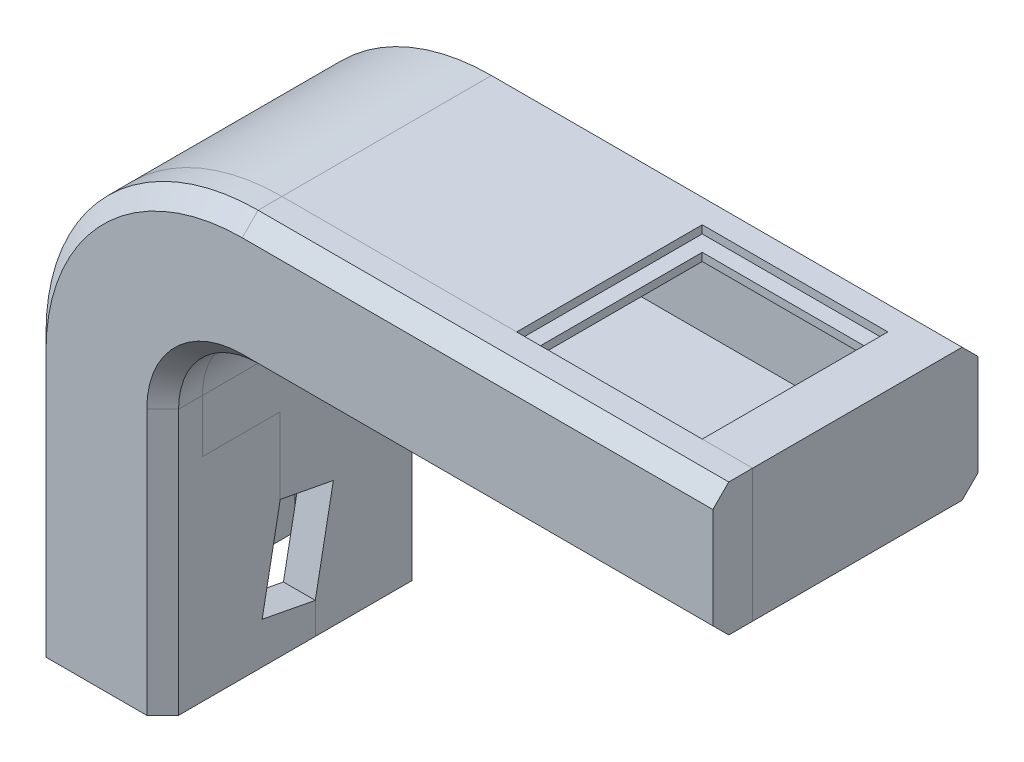
SolidWorks part; units mm, degrees
ref_plane "Front Plane" through (0, 0, 0) normal (0, 0, 1) x (1, 0, 0)
ref_plane "Top Plane" through (0, 0, 0) normal (0, 1, 0) x (1, 0, 0)
ref_plane "Right Plane" through (0, 0, 0) normal (1, 0, 0) x (0, 0, -1)
sketch "Sketch1" plane through (0, 0, 0) normal (0, 0, 1) x (1, 0, 0)
  line L1 (-76.75, 10) -> (-101.75, 10)
  line L2 (-76.75, 10) -> (-76.75, 100)
  line L3 (-76.75, 100) -> (-101.75, 100)
  line L4 (-101.75, 10) -> (-101.75, 100)
  line L5 (-76.75, 100) -> (27, 100)
  line L6 (-76.75, 100) -> (-76.75, 75)
  line L7 (-76.75, 75) -> (27, 75)
  line L8 (27, 100) -> (27, 75)
  dimension "D1" = 10
  dimension "D2" = 25
  dimension "D3" = 75
  dimension "D4" = 76.75
  dimension "D5" = 27
extrude "Boss-Extrude1" add sketch "Sketch1" along normal mid plane 50 contours L4 L1 L2 L3 | L8 L5 L2 L7 region at (-89.25, 55, 0) region at (-24.875, 87.5, 0)
fillet "Fillet2" radius 15 1 edges at (-76.75, 75, 0)
fillet "Fillet3" radius 40 1 edges at (-101.75, 100, 0)
fillet "Fillet1" radius 3 12 edges at (-17.375, 75, -25) (-17.375, 100, -25) (-17.375, 100, 25) (-17.375, 75, 25) (-101.75, 35, -25) (-101.75, 35, 25) (-76.75, 35, -25) (-76.75, 35, 25) (-90.0343, 88.2843, -25) (-90.0343, 88.2843, 25) (-72.3566, 70.6066, -25) (-72.3566, 70.6066, 25) profile chamfer
shell "Shell1" thickness 6 removed face at (-89.25, 10, 0)
sketch "Sketch2" plane through (-101.75, 0, 0) normal (-1, 0, 0) x (0, 0, 1)
  line L0 (-7.0749, 33.6959) -> (-5.199, 23.8734) construction
  line L1 (-5.6628, 15.6403) -> (8.0887, 18.2666) construction
  line L2 (4.6235, 25.7494) -> (2.7475, 35.5718) construction
  line L8 (11.8506, 16.9489) -> (9.9747, 26.7714) construction
  line L9 (9.9747, 26.7714) -> (-9.6702, 23.0195) construction
  line L10 (-9.6702, 23.0195) -> (-7.7943, 13.197) construction
  line L11 (-7.7943, 13.197) -> (11.8506, 16.9489) construction
  line L12 (9.9747, 26.7714) -> (8.0988, 36.5938) construction
  line L13 (8.0988, 36.5938) -> (-11.5462, 32.842) construction
  line L14 (-11.5462, 32.842) -> (-9.6702, 23.0195) construction
  line L15 (-9.6702, 23.0195) -> (9.9747, 26.7714) construction
  line L16 (-3.7777, 15.8985) -> (6.2412, 17.8119)
  line L17 (-3.7777, 15.8985) -> (-7.1919, 33.7754)
  line L18 (6.2412, 17.8119) -> (2.827, 35.6888)
  line L19 (-7.1919, 33.7754) -> (2.827, 35.6888)
  line L20 (-2.1637, 34.6339) -> (-2.1825, 34.7321) construction
  dimension "D1" = 0.1
  dimension "D2" = 0.1
  dimension "D3" = 0.1
  dimension "D4" = 0.1
extrude "Cut-Extrude1" cut sketch "Sketch2" against normal through all
ref_axis "Axis1" through (0, 164.2594, 0) along (0, -1, 0)
sketch "Sketch3" plane through (0, 100, 0) normal (0, 1, 0) x (1, 0, 0)
  line L0 (27, -22) -> (27, 22) construction
  line L1 (17.5, 17.5) -> (-17.5, 17.5)
  line L2 (17.5, 17.5) -> (17.5, -17.5)
  line L3 (17.5, -17.5) -> (-17.5, -17.5)
  line L4 (-17.5, 17.5) -> (-17.5, -17.5)
  point P6 (17.5, 0)
  point P9 (0, 17.5)
  dimension "D1" = 9.5
  dimension "D2" = 35
extrude "Cut-Extrude2" cut sketch "Sketch3" against normal up to next
sketch "Sketch4" plane through (0, 0, -17.5) normal (0, 0, 1) x (1, 0, 0)
  line L0 (-17.5, 94) -> (-17.5, 100) construction
  line L1 (-21.6, 98.5) -> (21.6, 98.5)
  line L2 (-21.6, 98.5) -> (-21.6, 95.5)
  line L3 (-21.6, 95.5) -> (21.6, 95.5)
  line L4 (21.6, 98.5) -> (21.6, 95.5)
  line L6 (17.5, 94) -> (17.5, 100) construction
  point P8 (-17.5, 97)
  point P9 (-21.6, 97)
  dimension "D1" = 3
  dimension "D2" = 4.1
  dimension "D3" = 4.1
extrude "Cut-Extrude3" cut sketch "Sketch4" against normal blind 4.1 and the other way blind 39.1
sketch "Sketch5" plane through (0, 75, 0) normal (0, -1, 0) x (1, 0, 0)
  line L0 (-22.0202, 9) -> (-20.0202, 9) construction
  line L1 (-22.0202, 10.15) -> (-20.0202, 10.15)
  line L2 (-22.0202, 7.85) -> (-20.0202, 7.85)
  line L3 (-22.0202, -9) -> (-20.0202, -9) construction
  line L4 (-22.0202, -7.85) -> (-20.0202, -7.85)
  line L5 (-22.0202, -10.15) -> (-20.0202, -10.15)
  arc A0 (-22.0202, 10.15) -> (-22.0202, 7.85) centre (-22.0202, 9) ccw
  arc A1 (-20.0202, 7.85) -> (-20.0202, 10.15) centre (-20.0202, 9) ccw
  circle A2 centre (-21.0202, -9) radius 1 construction
  circle A3 centre (-21.0202, 9) radius 1 construction
  arc A4 (-22.0202, -7.85) -> (-22.0202, -10.15) centre (-22.0202, -9) ccw
  arc A5 (-20.0202, -10.15) -> (-20.0202, -7.85) centre (-20.0202, -9) ccw
  point P6 (-21.0202, 9)
  point P12 (-21.0202, -9)
  dimension "D1" = 2.3
  dimension "D2" = 2
sketch "Sketch6" plane through (-101.75, 0, 0) normal (-1, 0, 0) x (0, 0, 1)
  line L0 (-3.7777, 10) -> (-3.7777, 15.8985)
  line L1 (22, 10) -> (-22, 10) construction
  line L2 (-3.7777, 15.8985) -> (2.827, 35.6888)
  line L3 (2.827, 35.6888) -> (2.827, 50)
  line L4 (2.827, 50) -> (17.5, 50)
  line L5 (17.5, 50) -> (17.5, 116.7947)
  line L6 (22, 10) -> (22, 60) construction
  dimension "D1" = 4.5
  dimension "D2" = 40
split "Split1" trim tools "Sketch6" bodies to split 104 resulting bodies 107 108
